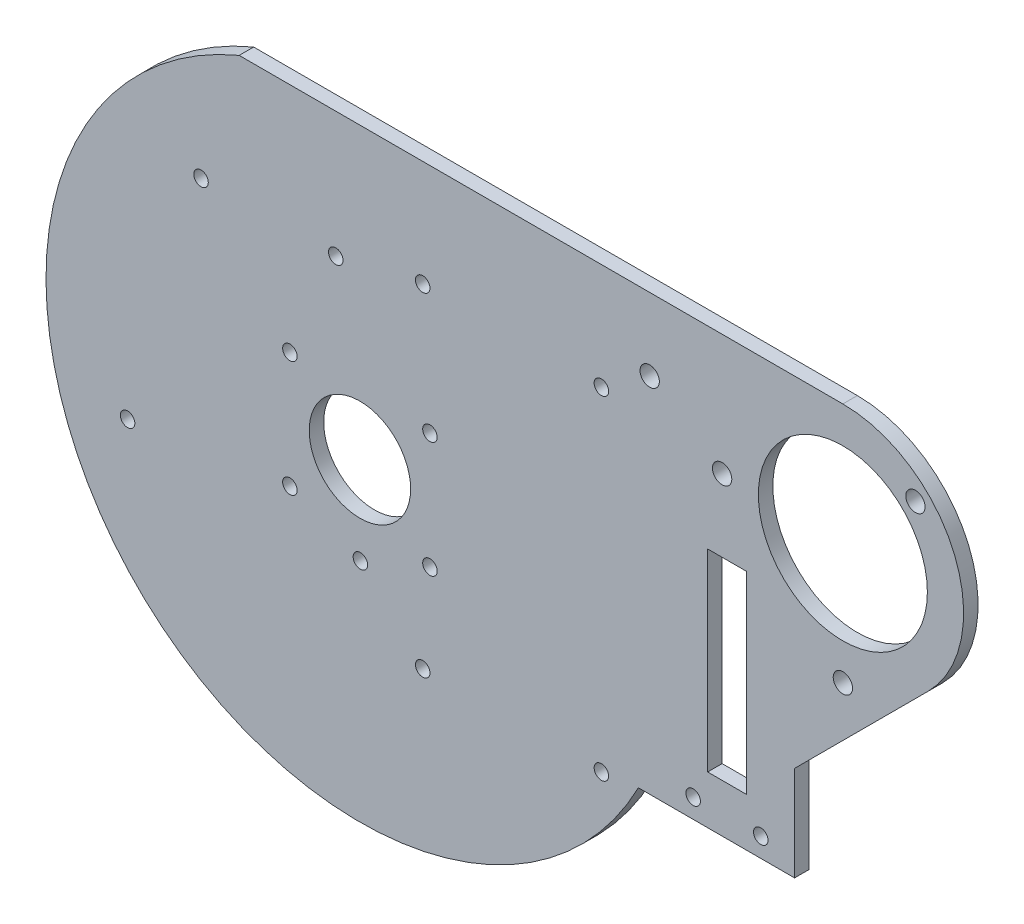
SolidWorks part; units mm, degrees
ref_plane "前视基准面" through (0, 0, 0) normal (0, 0, 1) x (1, 0, 0)
ref_plane "上视基准面" through (0, 0, 0) normal (0, 1, 0) x (1, 0, 0)
ref_plane "右视基准面" through (0, 0, 0) normal (1, 0, 0) x (0, 0, -1)
sketch "Sketch1" plane through (0, 0, 0) normal (0, 0, 1) x (1, 0, 0)
  line L0 (-10.9179, 60) -> (113.3582, 60) construction
  line L3 (-33.1662, 50) -> (-60, 50)
  line L4 (-60, 0) -> (-60, 50)
  line L6 (67.51, -32.8453) -> (81.2655, -19.0899) construction
  line L7 (90, -10.3553) -> (117.6777, 17.3223)
  line L12 (76, 7.9315) -> (76, -17.4174) construction
  line L13 (0, 60) -> (100, 60)
  line L15 (72, 20) -> (80, 20)
  line L16 (72, 20) -> (72, -20)
  line L17 (72, -20) -> (80, -20)
  line L18 (80, 20) -> (80, -20)
  line L19 (72, 20) -> (80, -20) construction
  line L20 (72, -20) -> (80, 20) construction
  line L23 (90, -30) -> (56.5685, -30)
  line L24 (90, -30) -> (90, -10.3553)
  line L25 (56.5685, -30) -> (51.9615, -30)
  line L26 (57.5608, -26) -> (84.9155, -26) construction
  arc A0 (0, 60) -> (51.9615, -30) centre (0, 0) ccw
  circle A2 centre (0, 0) radius 10.5
  arc A8 (117.6777, 17.3223) -> (100, 60) centre (100, 35) ccw
  circle A9 centre (100, 35) radius 17.5
  circle A10 centre (69, -26) radius 1.5
  circle A11 centre (83, -26) radius 1.5
  point P18 (76, 0)
  dimension "D1" = 120
  dimension "D2" = 136
  dimension "D3" = 21
  dimension "D5" = 50
  dimension "D4" = 100
  dimension "D6" = 35
  dimension "D13" = 7
  dimension "D7" = 10
  dimension "D8" = 8
  dimension "D9" = 40
  dimension "D10" = 90
  dimension "D11" = 150
  dimension "D12" = 6
extrude "Boss-Extrude1" add sketch "Sketch1" along normal blind 3 contours A0 L3 L4 | A0 A2 region at (-52.3919, 38.1269, 0) region at (20.0408, 6.3076, 0)
sketch "Sketch2" plane through (0, 0, 3) normal (0, 0, 1) x (1, 0, 0)
  line L1 (-60, 0) -> (-60, 50) construction
  line L2 (0, 60) -> (100, 60) construction
  circle A1 centre (0, 0) radius 57
  circle A2 centre (60, 45) radius 2
  circle A6 centre (100, 35) radius 14
  dimension "D1" = 15
  dimension "D5" = 28
  dimension "D2" = 120
extrude "Cut-Extrude1" cut sketch "Sketch2" against normal up to next contours A2
sketch "Sketch3" plane through (0, 0, 3) normal (0, 0, 1) x (1, 0, 0)
  line L0 (117.6777, 52.6777) -> (112.3744, 47.3744) construction
  circle A0 centre (100, 35) radius 17.5 construction
  circle A1 centre (100, 35) radius 25 construction
  circle A2 centre (100, 10) radius 2
  circle A3 centre (75, 35) radius 2
  circle A4 centre (115.026, 50.026) radius 2
  dimension "D1" = 35
extrude "Cut-Extrude2" cut sketch "Sketch3" against normal up to next
sketch "Sketch4" plane through (0, 0, 3) normal (0, 0, 1) x (1, 0, 0)
  circle A0 centre (0, 0) radius 60
  circle A1 centre (0, 0) radius 65
extrude "Boss-Extrude2" add sketch "Sketch4" against normal up to surface (3 mm away) up to face at (102, 10, 0)
sketch "Sketch5" plane through (0, 0, 3) normal (0, 0, 1) x (1, 0, 0)
  line L1 (-60, 50) -> (-41.5331, 50)
  line L2 (-60, 50) -> (-60, 25)
  arc A0 (-41.5331, 50) -> (-60, 25) centre (0, 0) ccw
extrude "Cut-Extrude3" cut sketch "Sketch5" against normal blind 10
sketch "Sketch6" plane through (0, 0, 3) normal (0, 0, 1) x (1, 0, 0)
  line L0 (25, 60) -> (-25, 60)
  arc A0 (25, 60) -> (57.6628, -30) centre (0, 0) ccw construction
  arc A1 (-25, 60) -> (25, 60) centre (0, 0) cw
extrude "Cut-Extrude4" cut sketch "Sketch6" against normal blind 10
sketch "Sketch7" plane through (0, 0, 3) normal (0, 0, 1) x (1, 0, 0)
  circle A0 centre (-14.5, 12) radius 1.5
  circle A1 centre (14.5, 12) radius 1.5
  circle A2 centre (-14.5, -12) radius 1.5
  circle A3 centre (14.5, -12) radius 1.5
extrude "Cut-Extrude5" cut sketch "Sketch7" against normal up to next
sketch "Sketch8" plane through (0, 0, 3) normal (0, 0, 1) x (1, 0, 0)
  line L0 (-25, 60) -> (100, 60) construction
  line L1 (90, -30) -> (90, -10.3553) construction
  circle A0 centre (50, 38) radius 1.5
  circle A1 centre (13, 38) radius 1.5
  circle A2 centre (50, -31) radius 1.5
  circle A3 centre (13, -31) radius 1.5
  circle A4 centre (-5, 34) radius 1.5
  circle A6 centre (-32.9, 34) radius 1.5
  circle A7 centre (0.1, -18.1) radius 1.5
  circle A8 centre (-48.1, -16.8) radius 1.5
  dimension "D1" = 22
  dimension "D2" = 40
  dimension "D3" = 37
  dimension "D4" = 69
  dimension "D6" = 26
  dimension "D8" = 27.9
  dimension "D9" = 5.1
  dimension "D11" = 15.2
  dimension "D12" = 1.3
  dimension "D5" = 69
  dimension "D7" = 95
  dimension "D10" = 50.8
extrude "Cut-Extrude6" cut sketch "Sketch8" against normal up to next
